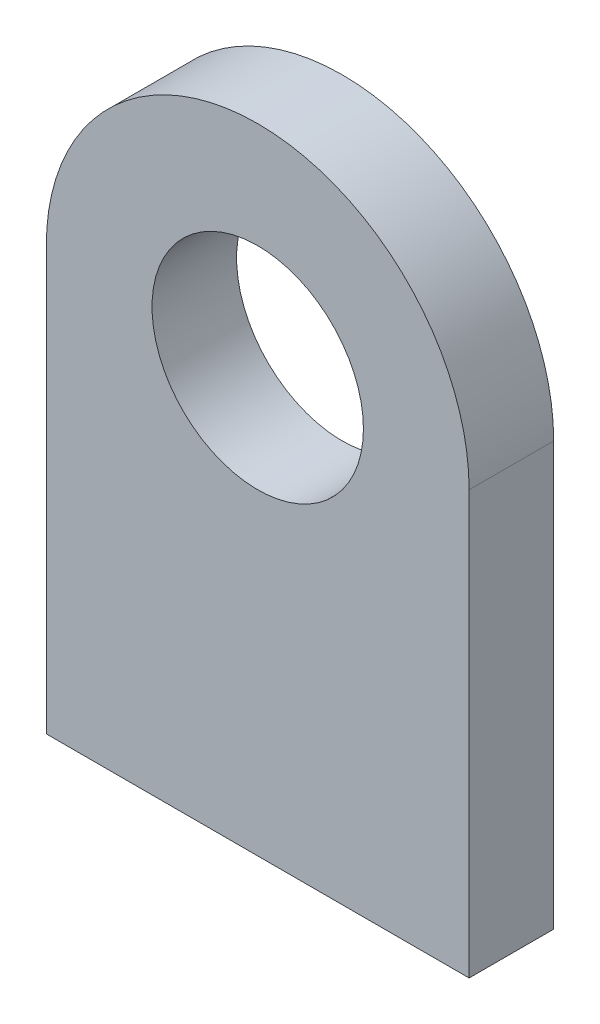
SolidWorks part; units mm, degrees
material "1060 Alloy"
ref_plane "Front Plane" through (0, 0, 0) normal (0, 0, 1) x (1, 0, 0)
ref_plane "Top Plane" through (0, 0, 0) normal (0, 1, 0) x (1, 0, 0)
ref_plane "Right Plane" through (0, 0, 0) normal (1, 0, 0) x (0, 0, -1)
sketch "Sketch1" plane through (0, 0, 0) normal (0, 0, 1) x (1, 0, 0)
  line L0 (0, 19.8538) -> (0, -21.8392) construction
  line L1 (-24.6755, 0) -> (26.59, 0) construction
  line L4 (-6.35, 0) -> (-6.35, -12.7)
  line L5 (-6.35, -12.7) -> (6.35, -12.7)
  line L6 (6.35, 0) -> (6.35, -12.7)
  line L7 (-2.8398, 5.6796) -> (6.35, -12.7) construction
  line L8 (-6.35, -12.7) -> (2.8398, 5.6796) construction
  circle A0 centre (0, 0) radius 3.175
  arc A1 (6.35, 0) -> (-6.35, 0) centre (0, 0) ccw
  point P12 (-6.35, 0)
  point P13 (0, 0)
  dimension "D1" = 6.35
  dimension "D2" = 12.7
  dimension "D3" = 12.7
extrude "Boss-Extrude1" add sketch "Sketch1" along normal blind 2.54
sketch "Sketch2" plane through (0, 0, 2.54) normal (0, 0, 1) x (1, 0, 0)
  line L0 (0, 12.118) -> (0, -18.5266) construction
